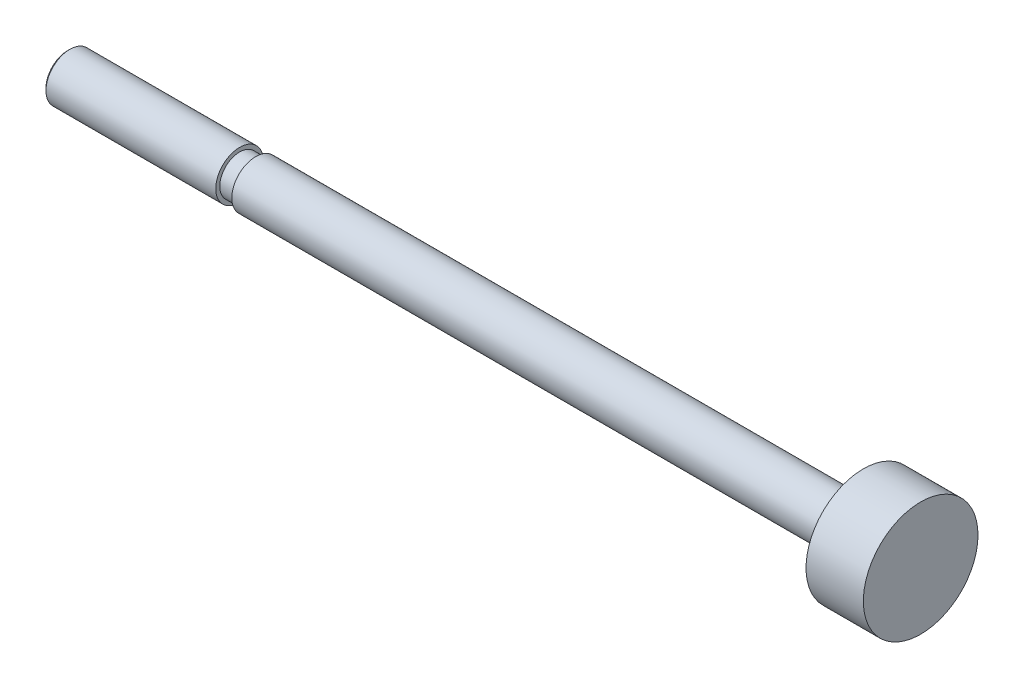
SolidWorks part; units mm, degrees
ref_plane "Front Plane" through (0, 0, 0) normal (0, 0, 1) x (1, 0, 0)
ref_plane "Top Plane" through (0, 0, 0) normal (0, 1, 0) x (1, 0, 0)
ref_plane "Right Plane" through (0, 0, 0) normal (1, 0, 0) x (0, 0, -1)
sketch "Sketch1" plane through (0, 0, 0) normal (1, 0, 0) x (0, 0, -1)
  circle A0 centre (0, 0) radius 5
  circle A1 centre (0, 0) radius 2.1827
  circle A2 centre (0, 0) radius 1.9328
  circle A3 centre (0, 0) radius 1.7328
  circle A4 centre (0, 0) radius 2.0828
extrude "Boss-Extrude2" add sketch "Sketch1" against normal blind 5 contours A3 | A2 A3 | A4 A2 | A1 A4 | A0 A1 region at (0, 0, 4.8586) region at (0, 0, 2.121) region at (0, 0, 1.8781) region at (0, 0, 0) region at (0, 0, 2.0239)
extrude "Boss-Extrude3" add sketch "Sketch1<5>" against normal blind 57.9999 contours A4
sketch "Sketch1<5>" plane through (0, 0, 0) normal (1, 0, 0) x (0, 0, -1) same geometry as "Sketch1"
extrude "Boss-Extrude4" add sketch "Sketch1<6>" against normal blind 0.1999 from surface contours A2 starting at face at (-57.9999, 0, -2.0828)
sketch "Sketch1<6>" plane through (0, 0, 0) normal (1, 0, 0) x (0, 0, -1) same geometry as "Sketch1"
extrude "Boss-Extrude5" add sketch "Sketch1<7>" against normal blind 1.1999 from surface contours A3 starting at face at (-58.1998, 0, -1.9328)
sketch "Sketch1<7>" plane through (0, 0, 0) normal (1, 0, 0) x (0, 0, -1) same geometry as "Sketch1"
extrude "Boss-Extrude6" add sketch "Sketch1<8>" against normal blind 15 from surface contours A4 starting at face at (-59.3997, 0, -1.7328)
sketch "Sketch1<8>" plane through (0, 0, 0) normal (1, 0, 0) x (0, 0, -1) same geometry as "Sketch1"
chamfer "Chamfer1" distance 0.2032 angle 45 1 edges at (-58.1998, 0, -1.9328)
chamfer "Chamfer2" distance 0.1905 angle 45 1 edges at (-74.3996, 0, -2.0828)
equation "\"D2@Sketch1\"=.164 + .00787"
equation "\"D1@Boss-Extrude3\"=1.66in + .7874 - 0.16394"
equation "\"D3@Sketch1\"=0.17187in - 0.01968"
equation "\"D4@Sketch1\"=\"D3@Sketch1\" - .01575"
